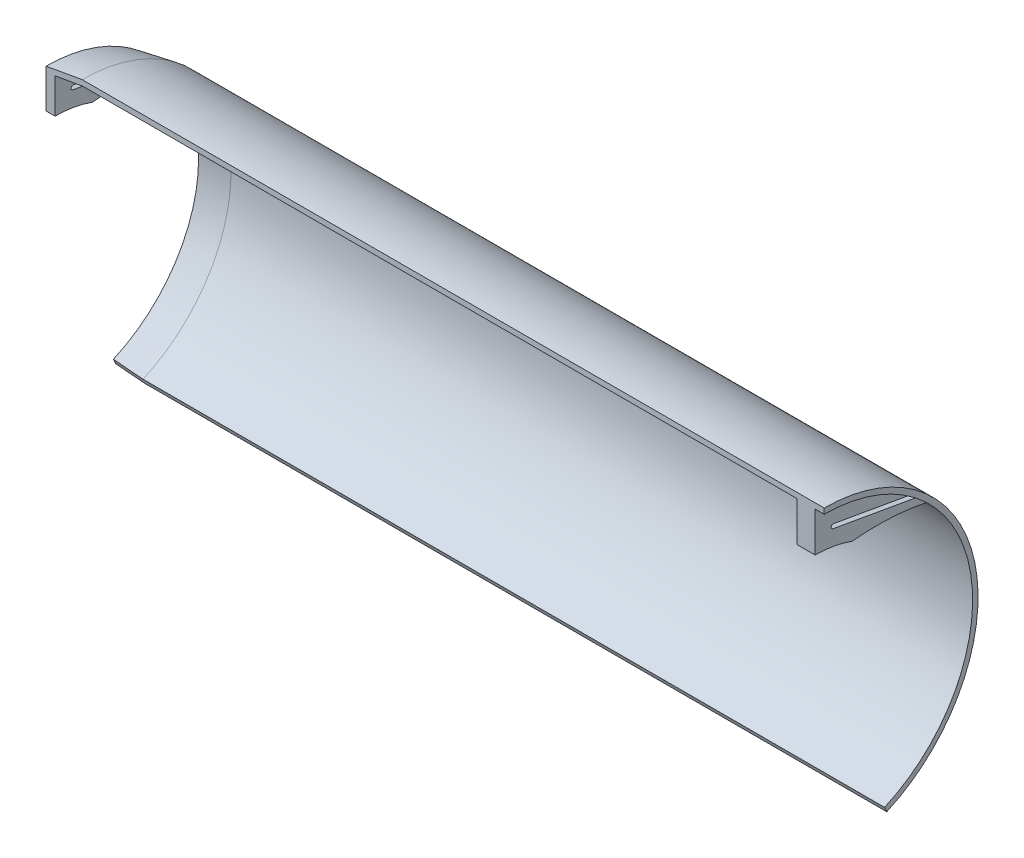
SolidWorks part; units mm, degrees
ref_plane "Front Plane" through (0, 0, 0) normal (0, 0, 1) x (1, 0, 0)
ref_plane "Top Plane" through (0, 0, 0) normal (0, 1, 0) x (1, 0, 0)
ref_plane "Right Plane" through (0, 0, 0) normal (1, 0, 0) x (0, 0, -1)
curve "Curve1"
  spline degree 3 poles (0, 0, 0) (-0.0123, 3.8916, 0) (-0.0274, 8.685, 0) (0.3616, 14.0857, 0) (0.5761, 16.0905, 0) (0.7825, 17.6048, 0) (0.9862, 18.8543, 0) (1.1887, 19.9315, 0) (1.3904, 20.8857, 0) (1.5917, 21.7465, 0) (1.7927, 22.5337, 0) (1.9935, 23.2611, 0) (2.1942, 23.9386, 0) (2.3947, 24.5739, 0) (2.5952, 25.1728, 0) (2.7956, 25.7401, 0) (2.9959, 26.2796, 0) (3.1962, 26.7943, 0) (3.3965, 27.2868, 0) (3.5967, 27.7594, 0) (3.7969, 28.2139, 0) (3.9971, 28.6519, 0) (4.1973, 29.0748, 0) (4.3974, 29.4838, 0) (4.5976, 29.8799, 0) (4.7977, 30.2641, 0) (4.9978, 30.6373, 0) (5.1979, 31.0001, 0) (5.398, 31.3533, 0) (5.5981, 31.6974, 0) (5.7982, 32.033, 0) (5.9983, 32.3606, 0) (6.1984, 32.6807, 0) (6.3985, 32.9935, 0) (6.5985, 33.2996, 0) (6.7986, 33.5993, 0) (6.9986, 33.8929, 0) (7.1987, 34.1806, 0) (7.3987, 34.4628, 0) (7.5988, 34.7397, 0) (7.7988, 35.0115, 0) (7.9989, 35.2785, 0) (8.1989, 35.5408, 0) (8.399, 35.7988, 0) (8.599, 36.0524, 0) (8.799, 36.3019, 0) (8.9991, 36.5476, 0) (9.1991, 36.7894, 0) (9.3991, 37.0275, 0) (9.5992, 37.2622, 0) (9.7992, 37.4934, 0) (9.9992, 37.7214, 0) (10.1992, 37.9461, 0) (10.3993, 38.1679, 0) (10.5993, 38.3866, 0) (10.7993, 38.6025, 0) (10.9993, 38.8156, 0) (11.1993, 39.026, 0) (11.3994, 39.2338, 0) (11.5994, 39.4391, 0) (11.7994, 39.6419, 0) (11.9994, 39.8422, 0) (12.1994, 40.0403, 0) (12.3995, 40.2361, 0) (12.5995, 40.4297, 0) (12.7995, 40.6212, 0) (12.9995, 40.8106, 0) (13.1995, 40.998, 0) (13.3995, 41.1834, 0) (13.5995, 41.3668, 0) (13.7995, 41.5484, 0) (13.9996, 41.7281, 0) (14.1996, 41.9061, 0) (14.3996, 42.0823, 0) (14.5996, 42.2568, 0) (14.7996, 42.4296, 0) (14.9996, 42.6008, 0) (15.1996, 42.7705, 0) (15.3996, 42.9385, 0) (15.5996, 43.1051, 0) (15.7996, 43.2701, 0) (15.9997, 43.4337, 0) (16.1997, 43.5959, 0) (16.3997, 43.7567, 0) (16.5997, 43.9161, 0) (16.7997, 44.0742, 0) (16.9997, 44.2309, 0) (17.1997, 44.3864, 0) (17.3997, 44.5406, 0) (17.5997, 44.6936, 0) (17.7997, 44.8453, 0) (17.9997, 44.9959, 0) (18.1997, 45.1453, 0) (18.3997, 45.2936, 0) (18.5997, 45.4407, 0) (18.7997, 45.5868, 0) (18.9997, 45.7317, 0) (19.1998, 45.8756, 0) (19.3998, 46.0185, 0) (19.5998, 46.1603, 0) (19.7998, 46.3011, 0) (19.9998, 46.4409, 0) (20.1998, 46.5797, 0) (20.3998, 46.7176, 0) (20.5998, 46.8546, 0) (20.7998, 46.9906, 0) (20.9998, 47.1257, 0) (21.1998, 47.2599, 0) (21.3998, 47.3932, 0) (21.5998, 47.5256, 0) (21.7998, 47.6572, 0) (21.9998, 47.788, 0) (22.1998, 47.9179, 0) (22.3998, 48.047, 0) (22.5998, 48.1753, 0) (22.7998, 48.3028, 0) (22.9998, 48.4295, 0) (23.1998, 48.5555, 0) (23.3998, 48.6807, 0) (23.5998, 48.8051, 0) (23.7998, 48.9288, 0) (23.9998, 49.0518, 0) (24.1998, 49.1741, 0) (24.3998, 49.2957, 0) (24.5998, 49.4165, 0) (24.7999, 49.5367, 0) (24.9999, 49.6562, 0) (25.1999, 49.7751, 0) (25.3999, 49.8933, 0) (25.5999, 50.0108, 0) (25.7999, 50.1277, 0) (25.9999, 50.2439, 0) (26.1999, 50.3596, 0) (26.3999, 50.4746, 0) (26.5999, 50.589, 0) (26.7999, 50.7028, 0) (26.9999, 50.8161, 0) (27.1999, 50.9287, 0) (27.3999, 51.0407, 0) (27.5999, 51.1522, 0) (27.7999, 51.2631, 0) (27.9999, 51.3735, 0) (28.1999, 51.4833, 0) (28.3999, 51.5926, 0) (28.5999, 51.7013, 0) (28.7999, 51.8095, 0) (28.9999, 51.9172, 0) (29.1999, 52.0243, 0) (29.3999, 52.131, 0) (29.5999, 52.2371, 0) (29.7999, 52.3428, 0) (29.9999, 52.4479, 0) (30.1999, 52.5526, 0) (30.3999, 52.6567, 0) (30.5999, 52.7604, 0) (30.7999, 52.8636, 0) (30.9999, 52.9664, 0) (31.1999, 53.0687, 0) (31.3999, 53.1705, 0) (31.5999, 53.2719, 0) (31.7999, 53.3728, 0) (31.9999, 53.4733, 0) (32.1999, 53.5733, 0) (32.3999, 53.6729, 0) (32.5999, 53.7721, 0) (32.7999, 53.8709, 0) (32.9999, 53.9692, 0) (33.1999, 54.0671, 0) (33.3999, 54.1646, 0) (33.5999, 54.2617, 0) (33.7999, 54.3584, 0) (33.9999, 54.4547, 0) (34.1999, 54.5506, 0) (34.3999, 54.6461, 0) (34.5999, 54.7412, 0) (34.7999, 54.836, 0) (34.9999, 54.9303, 0) (35.1999, 55.0243, 0) (35.3999, 55.1179, 0) (35.5999, 55.2111, 0) (35.7999, 55.304, 0) (35.9999, 55.3965, 0) (36.1999, 55.4887, 0) (36.3999, 55.5805, 0) (36.5999, 55.6719, 0) (36.7999, 55.763, 0) (36.9999, 55.8537, 0) (37.1999, 55.9441, 0) (37.3999, 56.0342, 0) (37.5999, 56.1239, 0) (37.7999, 56.2133, 0) (37.9999, 56.3024, 0) (38.1999, 56.3911, 0) (38.3999, 56.4795, 0) (38.5999, 56.5676, 0) (38.7999, 56.6554, 0) (38.9999, 56.7428, 0) (39.1999, 56.83, 0) (39.3999, 56.9168, 0) (39.5999, 57.0033, 0) (39.7999, 57.0896, 0) (39.9999, 57.1755, 0) (40.1999, 57.2611, 0) (40.3999, 57.3464, 0) (40.5999, 57.4314, 0) (40.7999, 57.5161, 0) (40.9999, 57.6006, 0) (41.1999, 57.6847, 0) (41.3999, 57.7686, 0) (41.6, 57.8522, 0) (41.8, 57.9355, 0) (42, 58.0185, 0) (42.2, 58.1012, 0) (42.4, 58.1837, 0) (42.6, 58.2659, 0) (42.8, 58.3479, 0) (43, 58.4295, 0) (43.2, 58.5109, 0) (43.4, 58.592, 0) (43.6, 58.6729, 0) (43.8, 58.7535, 0) (44, 58.8339, 0) (44.2, 58.914, 0) (44.4, 58.9938, 0) (44.6, 59.0734, 0) (44.8, 59.1528, 0) (45, 59.2319, 0) (45.2, 59.3107, 0) (45.4, 59.3893, 0) (45.6, 59.4677, 0) (45.8, 59.5458, 0) (46, 59.6237, 0) (46.2, 59.7014, 0) (46.4, 59.7788, 0) (46.6, 59.856, 0) (46.8, 59.9329, 0) (47, 60.0096, 0) (47.2, 60.0861, 0) (47.4, 60.1624, 0) (47.6, 60.2385, 0) (47.8, 60.3143, 0) (48, 60.3899, 0) (48.2, 60.4652, 0) (48.4, 60.5404, 0) (48.6, 60.6153, 0) (48.8, 60.6901, 0) (49, 60.7646, 0) (49.2, 60.8389, 0) (49.4, 60.913, 0) (49.6, 60.9869, 0) (49.8, 61.0605, 0) (50, 61.134, 0) (50.2, 61.2072, 0) (50.4, 61.2803, 0) (50.6, 61.3531, 0) (50.8, 61.4258, 0) (51, 61.4982, 0) (51.2, 61.5705, 0) (51.4, 61.6426, 0) (51.6, 61.7144, 0) (51.8, 61.7861, 0) (52, 61.8575, 0) (52.2, 61.9288, 0) (52.4, 61.9999, 0) (52.6, 62.0708, 0) (52.8, 62.1415, 0) (53, 62.212, 0) (53.2, 62.2824, 0) (53.4, 62.3525, 0) (53.6, 62.4225, 0) (53.8, 62.4923, 0) (54, 62.5619, 0) (54.2, 62.6313, 0) (54.4, 62.7006, 0) (54.6, 62.7696, 0) (54.8, 62.8385, 0) (55, 62.9072, 0) (55.2, 62.9758, 0) (55.4, 63.0441, 0) (55.6, 63.1123, 0) (55.8, 63.1803, 0) (56, 63.2482, 0) (56.2, 63.3159, 0) (56.4, 63.3834, 0) (56.6, 63.4507, 0) (56.8, 63.5179, 0) (57, 63.5849, 0) (57.2, 63.6518, 0) (57.4, 63.7185, 0) (57.6, 63.785, 0) (57.8, 63.8513, 0) (58, 63.9175, 0) (58.2, 63.9836, 0) (58.4, 64.0495, 0) (58.6, 64.1152, 0) (58.8, 64.1808, 0) (59, 64.2462, 0) (59.2, 64.3114, 0) (59.4, 64.3765, 0) (59.6, 64.4415, 0) (59.8, 64.5063, 0) (60, 64.5709, 0) (60.2, 64.6354, 0) (60.4, 64.6998, 0) (60.6, 64.764, 0) (60.8, 64.828, 0) (61, 64.8919, 0) (61.2, 64.9557, 0) (61.4, 65.0193, 0) (61.6, 65.0827, 0) (61.8, 65.1461, 0) (62, 65.2092, 0) (62.2, 65.2723, 0) (62.4, 65.3352, 0) (62.6, 65.3979, 0) (62.8, 65.4605, 0) (63, 65.523, 0) (63.2, 65.5853, 0) (63.4, 65.6475, 0) (63.6, 65.7096, 0) (63.8, 65.7715, 0) (64, 65.8333, 0) (64.2, 65.895, 0) (64.4, 65.9565, 0) (64.6, 66.0179, 0) (64.8, 66.0791, 0) (65, 66.1402, 0) (65.2, 66.2012, 0) (65.4, 66.2621, 0) (65.6, 66.3228, 0) (65.8, 66.3834, 0) (66, 66.4439, 0) (66.2, 66.5042, 0) (66.4, 66.5644, 0) (66.6, 66.6245, 0) (66.8, 66.6845, 0) (67, 66.7443, 0) (67.2, 66.804, 0) (67.4, 66.8636, 0) (67.6, 66.923, 0) (67.8, 66.9824, 0) (68, 67.0416, 0) (68.2, 67.1007, 0) (68.4, 67.1597, 0) (68.6, 67.2185, 0) (68.8, 67.2772, 0) (69, 67.3359, 0) (69.2, 67.3943, 0) (69.4, 67.4527, 0) (69.6, 67.511, 0) (69.8, 67.5691, 0) (70, 67.6271, 0) (70.2, 67.6851, 0) (70.4, 67.7428, 0) (70.6, 67.8005, 0) (70.8, 67.8581, 0) (71, 67.9155, 0) (71.2, 67.9729, 0) (71.4, 68.0301, 0) (71.6, 68.0872, 0) (71.8, 68.1442, 0) (72, 68.2011, 0) (72.2, 68.2579, 0) (72.4, 68.3145, 0) (72.6, 68.3711, 0) (72.8, 68.4276, 0) (73, 68.4839, 0) (73.2, 68.5401, 0) (73.4, 68.5963, 0) (73.6, 68.6523, 0) (73.8, 68.7082, 0) (74, 68.764, 0) (74.2, 68.8197, 0) (74.4, 68.8753, 0) (74.6, 68.9308, 0) (74.8, 68.9862, 0) (75, 69.0415, 0) (75.2, 69.0966, 0) (75.4, 69.1517, 0) (75.6, 69.2067, 0) (75.8, 69.2616, 0) (76, 69.3164, 0) (76.2, 69.371, 0) (76.4, 69.4256, 0) (76.6, 69.4801, 0) (76.8, 69.5344, 0) (77, 69.5887, 0) (77.2, 69.6429, 0) (77.4, 69.697, 0) (77.6, 69.751, 0) (77.8, 69.8048, 0) (78, 69.8586, 0) (78.2, 69.9123, 0) (78.4, 69.9659, 0) (78.6, 70.0194, 0) (78.8, 70.0728, 0) (79, 70.1261, 0) (79.2, 70.1793, 0) (79.4, 70.2324, 0) (79.6, 70.2855, 0) (79.8, 70.3384, 0) (80, 70.3912, 0) (80.2, 70.444, 0) (80.4, 70.4966, 0) (80.6, 70.5492, 0) (80.8, 70.6017, 0) (81, 70.6541, 0) (81.2, 70.7064, 0) (81.4, 70.7586, 0) (81.6, 70.8107, 0) (81.8, 70.8627, 0) (82, 70.9146, 0) (82.2, 70.9665, 0) (82.4, 71.0182, 0) (82.6, 71.0699, 0) (82.8, 71.1215, 0) (83, 71.173, 0) (83.2, 71.2244, 0) (83.4, 71.2757, 0) (83.6, 71.3269, 0) (83.8, 71.3781, 0) (84, 71.4291, 0) (84.2, 71.4801, 0) (84.4, 71.531, 0) (84.6, 71.5818, 0) (84.8, 71.6325, 0) (85, 71.6832, 0) (85.2, 71.7337, 0) (85.4, 71.7842, 0) (85.6, 71.8346, 0) (85.8, 71.8849, 0) (86, 71.9351, 0) (86.2, 71.9853, 0) (86.4, 72.0354, 0) (86.6, 72.0853, 0) (86.8, 72.1352, 0) (87, 72.1851, 0) (87.2, 72.2348, 0) (87.4, 72.2845, 0) (87.6, 72.3341, 0) (87.8, 72.3836, 0) (88, 72.433, 0) (88.2, 72.4823, 0) (88.4, 72.5316, 0) (88.6, 72.5808, 0) (88.8, 72.6299, 0) (89, 72.6789, 0) (89.2, 72.7279, 0) (89.4, 72.7768, 0) (89.6, 72.8256, 0) (89.8, 72.8743, 0) (90, 72.923, 0) (90.2, 72.9716, 0) (90.4, 73.0201, 0) (90.6, 73.0685, 0) (90.8, 73.1168, 0) (91, 73.1651, 0) (91.2, 73.2133, 0) (91.4, 73.2614, 0) (91.6, 73.3095, 0) (91.8, 73.3575, 0) (92, 73.4054, 0) (92.2, 73.4532, 0) (92.4, 73.501, 0) (92.6, 73.5487, 0) (92.8, 73.5963, 0) (93, 73.6439, 0) (93.2, 73.6913, 0) (93.4, 73.7387, 0) (93.6, 73.7861, 0) (93.8, 73.8333, 0) (94, 73.8805, 0) (94.2, 73.9276, 0) (94.4, 73.9747, 0) (94.6, 74.0217, 0) (94.8, 74.0686, 0) (95, 74.1154, 0) (95.2, 74.1622, 0) (95.4, 74.2089, 0) (95.6, 74.2556, 0) (95.8, 74.3021, 0) (96, 74.3486, 0) (96.2, 74.3951, 0) (96.4, 74.4414, 0) (96.6, 74.4877, 0) (96.8, 74.534, 0) (97, 74.5801, 0) (97.2, 74.6262, 0) (97.4, 74.6723, 0) (97.6, 74.7182, 0) (97.8, 74.7641, 0) (98, 74.81, 0) (98.2, 74.8557, 0) (98.4, 74.9014, 0) (98.6, 74.9471, 0) (98.8, 74.9926, 0) (99, 75.0382, 0) (99.2, 75.0836, 0) (99.4, 75.129, 0) (99.6, 75.1743, 0) (99.8, 75.2196, 0) (100, 75.2647, 0) (100.2, 75.3099, 0) (100.4, 75.3549, 0) (100.6, 75.3999, 0) (100.8, 75.4449, 0) (101, 75.4898, 0) (101.2, 75.5346, 0) (101.4, 75.5793, 0) (101.6, 75.624, 0) (101.8, 75.6686, 0) (102, 75.7132, 0) (102.2, 75.7577, 0) (102.4, 75.8022, 0) (102.6, 75.8465, 0) (102.8, 75.8909, 0) (103, 75.9351, 0) (103.2, 75.9793, 0) (103.4, 76.0235, 0) (103.6, 76.0676, 0) (103.8, 76.1116, 0) (104, 76.1556, 0) (104.2, 76.1995, 0) (104.4, 76.2433, 0) (104.6, 76.2871, 0) (104.8, 76.3308, 0) (105, 76.3745, 0) (105.2, 76.4181, 0) (105.4, 76.4617, 0) (105.6, 76.5052, 0) (105.8, 76.5486, 0) (106, 76.592, 0) (106.2, 76.6353, 0) (106.4, 76.6786, 0) (106.6, 76.7218, 0) (106.8, 76.7649, 0) (107, 76.808, 0) (107.2, 76.8511, 0) (107.4, 76.8941, 0) (107.6, 76.937, 0) (107.8, 76.9799, 0) (108, 77.0227, 0) (108.2, 77.0655, 0) (108.4, 77.1082, 0) (108.6, 77.1508, 0) (108.8, 77.1934, 0) (109, 77.236, 0) (109.2, 77.2784, 0) (109.4, 77.3209, 0) (109.6, 77.3633, 0) (109.8, 77.4056, 0) (110, 77.4479, 0) (110.2, 77.4901, 0) (110.4, 77.5322, 0) (110.6, 77.5743, 0) (110.8, 77.6164, 0) (111, 77.6584, 0) (111.2, 77.7004, 0) (111.4, 77.7423, 0) (111.6, 77.7841, 0) (111.8, 77.8259, 0) (112, 77.8676, 0) (112.2, 77.9093, 0) (112.4, 77.951, 0) (112.6, 77.9925, 0) (112.8, 78.0341, 0) (113, 78.0756, 0) (113.2, 78.117, 0) (113.4, 78.1584, 0) (113.6, 78.1997, 0) (113.8, 78.241, 0) (114, 78.2822, 0) (114.2, 78.3234, 0) (114.4, 78.3645, 0) (114.6, 78.4056, 0) (114.8, 78.4466, 0) (115, 78.4876, 0) (115.2, 78.5285, 0) (115.4, 78.5694, 0) (115.6, 78.6102, 0) (115.8, 78.651, 0) (116, 78.6917, 0) (116.2, 78.7324, 0) (116.4, 78.773, 0) (116.6, 78.8136, 0) (116.8, 78.8541, 0) (117, 78.8946, 0) (117.2, 78.935, 0) (117.4, 78.9754, 0) (117.6, 79.0158, 0) (117.8, 79.0561, 0) (118, 79.0963, 0) (118.2, 79.1365, 0) (118.4, 79.1766, 0) (118.6, 79.2167, 0) (118.8, 79.2568, 0) (119, 79.2968, 0) (119.2, 79.3368, 0) (119.4, 79.3767, 0) (119.6, 79.4165, 0) (119.8, 79.4564, 0) (120, 79.4961, 0) (120.2, 79.5358, 0) (120.4, 79.5755, 0) (120.6, 79.6152, 0) (120.8, 79.6547, 0) (121, 79.6943, 0) (121.2, 79.7338, 0) (121.4, 79.7732, 0) (121.6, 79.8126, 0) (121.8, 79.852, 0) (122, 79.8913, 0) (122.2, 79.9306, 0) (122.4, 79.9698, 0) (122.6, 80.009, 0) (122.8, 80.0481, 0) (123, 80.0872, 0) (123.2, 80.1262, 0) (123.4, 80.1652, 0) (123.6, 80.2042, 0) (123.8, 80.2431, 0) (124, 80.282, 0) (124.2, 80.3208, 0) (124.4, 80.3596, 0) (124.6, 80.3983, 0) (124.8, 80.437, 0) (125, 80.4757, 0) (125.2, 80.5143, 0) (125.4, 80.5528, 0) (125.6, 80.5914, 0) (125.8, 80.6298, 0) (126, 80.6683, 0) (126.2, 80.7067, 0) (126.4, 80.745, 0) (126.6, 80.7833, 0) (126.8, 80.8216, 0) (127, 80.8598, 0) (127.2, 80.898, 0) (127.4, 80.9361, 0) (127.6, 80.9742, 0) (127.8, 81.0123, 0) (128, 81.0503, 0) (128.2, 81.0883, 0) (128.4, 81.1262, 0) (128.6, 81.1641, 0) (128.8, 81.2019, 0) (129, 81.2397, 0) (129.2, 81.2775, 0) (129.4, 81.3152, 0) (129.6, 81.3529, 0) (129.8, 81.3906, 0) (130, 81.4282, 0) (130.2, 81.4657, 0) (130.4, 81.5032, 0) (130.6, 81.5407, 0) (130.8, 81.5782, 0) (131, 81.6156, 0) (131.2, 81.6529, 0) (131.4, 81.6902, 0) (131.6, 81.7275, 0) (131.8, 81.7648, 0) (132, 81.802, 0) (132.2, 81.8391, 0) (132.4, 81.8763, 0) (132.6, 81.9133, 0) (132.8, 81.9504, 0) (133, 81.9874, 0) (133.2, 82.0244, 0) (133.4, 82.0613, 0) (133.6, 82.0982, 0) (133.8, 82.135, 0) (134, 82.1718, 0) (134.2, 82.2086, 0) (134.4, 82.2454, 0) (134.6, 82.282, 0) (134.8, 82.3187, 0) (135, 82.3553, 0) (135.2, 82.3919, 0) (135.4, 82.4285, 0) (135.6, 82.465, 0) (135.8, 82.5014, 0) (136, 82.5379, 0) (136.2, 82.5743, 0) (136.4, 82.6106, 0) (136.6, 82.6469, 0) (136.8, 82.6832, 0) (137, 82.7195, 0) (137.2, 82.7557, 0) (137.4, 82.7919, 0) (137.6, 82.828, 0) (137.8, 82.8641, 0) (138, 82.9001, 0) (138.2, 82.9362, 0) (138.4, 82.9722, 0) (138.6, 83.0081, 0) (138.8, 83.044, 0) (139, 83.0799, 0) (139.2, 83.1158, 0) (139.4, 83.1516, 0) (139.6, 83.1873, 0) (139.8, 83.2231, 0) (140, 83.2588, 0) (140.2, 83.2944, 0) (140.4, 83.3301, 0) (140.6, 83.3657, 0) (140.8, 83.4012, 0) (141, 83.4367, 0) (141.2, 83.4722, 0) (141.4, 83.5077, 0) (141.6, 83.5431, 0) (141.8, 83.5785, 0) (142, 83.6138, 0) (142.2, 83.6491, 0) (142.4, 83.6844, 0) (142.6, 83.7197, 0) (142.8, 83.7549, 0) (143, 83.79, 0) (143.2, 83.8252, 0) (143.4, 83.8603, 0) (143.6, 83.8954, 0) (143.8, 83.9304, 0) (144, 83.9654, 0) (144.2, 84.0004, 0) (144.4, 84.0353, 0) (144.6, 84.0702, 0) (144.8, 84.1051, 0) (145, 84.1399, 0) (145.2, 84.1747, 0) (145.4, 84.2095, 0) (145.6, 84.2442, 0) (145.8, 84.2789, 0) (146, 84.3136, 0) (146.2, 84.3482, 0) (146.4, 84.3828, 0) (146.6, 84.4174, 0) (146.8, 84.4519, 0) (147, 84.4864, 0) (147.2, 84.5209, 0) (147.4, 84.5553, 0) (147.6, 84.5897, 0) (147.8, 84.6241, 0) (148, 84.6584, 0) (148.2, 84.6927, 0) (148.4, 84.727, 0) (148.6, 84.7612, 0) (148.8, 84.7954, 0) (149, 84.8296, 0) (149.2, 84.8638, 0) (149.4, 84.8979, 0) (149.6, 84.9319, 0) (149.8, 84.966, 0) (149.9333, 84.9887, 0) (150, 85, 0) knots 0 0 0 0 0.061462 0.075706 0.085548 0.093322 0.099856 0.105554 0.110643 0.115268 0.119525 0.123482 0.127192 0.130691 0.13401 0.137173 0.140199 0.143104 0.145901 0.148602 0.151215 0.15375 0.156213 0.158609 0.160946 0.163227 0.165456 0.167638 0.169775 0.171871 0.173928 0.17595 0.177937 0.179893 0.181819 0.183716 0.185587 0.187433 0.189255 0.191054 0.192831 0.194589 0.196326 0.198045 0.199747 0.201431 0.2031 0.204753 0.206391 0.208015 0.209626 0.211223 0.212808 0.214381 0.215942 0.217493 0.219032 0.220561 0.22208 0.22359 0.225091 0.226582 0.228065 0.229539 0.231006 0.232464 0.233915 0.235359 0.236795 0.238225 0.239648 0.241065 0.242475 0.243879 0.245277 0.24667 0.248057 0.249438 0.250814 0.252185 0.253551 0.254913 0.256269 0.257621 0.258968 0.260311 0.26165 0.262984 0.264315 0.265641 0.266964 0.268282 0.269598 0.270909 0.272217 0.273522 0.274823 0.276121 0.277416 0.278707 0.279996 0.281281 0.282564 0.283843 0.28512 0.286394 0.287666 0.288935 0.290201 0.291465 0.292726 0.293985 0.295241 0.296495 0.297747 0.298996 0.300243 0.301489 0.302732 0.303972 0.305211 0.306448 0.307683 0.308916 0.310147 0.311376 0.312604 0.313829 0.315053 0.316275 0.317495 0.318714 0.319931 0.321147 0.32236 0.323573 0.324783 0.325993 0.3272 0.328406 0.329611 0.330815 0.332017 0.333217 0.334416 0.335614 0.336811 0.338006 0.3392 0.340393 0.341584 0.342775 0.343964 0.345152 0.346339 0.347524 0.348709 0.349892 0.351074 0.352256 0.353436 0.354615 0.355793 0.35697 0.358146 0.359321 0.360495 0.361668 0.36284 0.364011 0.365182 0.366351 0.36752 0.368687 0.369854 0.37102 0.372185 0.373349 0.374512 0.375674 0.376836 0.377997 0.379157 0.380316 0.381475 0.382632 0.383789 0.384946 0.386101 0.387256 0.38841 0.389563 0.390716 0.391868 0.393019 0.39417 0.39532 0.396469 0.397618 0.398766 0.399913 0.40106 0.402206 0.403351 0.404496 0.40564 0.406784 0.407927 0.409069 0.410211 0.411353 0.412493 0.413633 0.414773 0.415912 0.417051 0.418189 0.419326 0.420463 0.4216 0.422736 0.423871 0.425006 0.426141 0.427275 0.428408 0.429541 0.430674 0.431806 0.432937 0.434068 0.435199 0.436329 0.437459 0.438588 0.439717 0.440846 0.441974 0.443101 0.444229 0.445355 0.446482 0.447608 0.448733 0.449858 0.450983 0.452107 0.453231 0.454355 0.455478 0.456601 0.457723 0.458845 0.459967 0.461088 0.462209 0.46333 0.46445 0.46557 0.46669 0.467809 0.468928 0.470046 0.471164 0.472282 0.4734 0.474517 0.475634 0.47675 0.477866 0.478982 0.480098 0.481213 0.482328 0.483443 0.484557 0.485671 0.486785 0.487898 0.489011 0.490124 0.491237 0.492349 0.493461 0.494573 0.495684 0.496796 0.497906 0.499017 0.500127 0.501237 0.502347 0.503457 0.504566 0.505675 0.506784 0.507892 0.509001 0.510109 0.511216 0.512324 0.513431 0.514538 0.515645 0.516752 0.517858 0.518964 0.52007 0.521175 0.522281 0.523386 0.524491 0.525595 0.5267 0.527804 0.528908 0.530012 0.531116 0.532219 0.533322 0.534425 0.535528 0.53663 0.537733 0.538835 0.539937 0.541038 0.54214 0.543241 0.544342 0.545443 0.546544 0.547644 0.548745 0.549845 0.550945 0.552044 0.553144 0.554243 0.555342 0.556441 0.55754 0.558639 0.559737 0.560836 0.561934 0.563032 0.564129 0.565227 0.566324 0.567421 0.568518 0.569615 0.570712 0.571809 0.572905 0.574001 0.575097 0.576193 0.577289 0.578384 0.57948 0.580575 0.58167 0.582765 0.58386 0.584954 0.586049 0.587143 0.588237 0.589331 0.590425 0.591519 0.592612 0.593706 0.594799 0.595892 0.596985 0.598078 0.59917 0.600263 0.601355 0.602448 0.60354 0.604632 0.605724 0.606815 0.607907 0.608998 0.61009 0.611181 0.612272 0.613363 0.614453 0.615544 0.616635 0.617725 0.618815 0.619905 0.620995 0.622085 0.623175 0.624265 0.625354 0.626443 0.627533 0.628622 0.629711 0.6308 0.631888 0.632977 0.634066 0.635154 0.636242 0.637331 0.638419 0.639507 0.640594 0.641682 0.64277 0.643857 0.644945 0.646032 0.647119 0.648206 0.649293 0.65038 0.651467 0.652553 0.65364 0.654726 0.655813 0.656899 0.657985 0.659071 0.660157 0.661243 0.662328 0.663414 0.664499 0.665585 0.66667 0.667755 0.66884 0.669925 0.67101 0.672095 0.67318 0.674264 0.675349 0.676433 0.677518 0.678602 0.679686 0.68077 0.681854 0.682938 0.684022 0.685105 0.686189 0.687272 0.688356 0.689439 0.690522 0.691605 0.692688 0.693771 0.694854 0.695937 0.69702 0.698102 0.699185 0.700267 0.70135 0.702432 0.703514 0.704596 0.705678 0.70676 0.707842 0.708924 0.710006 0.711087 0.712169 0.71325 0.714332 0.715413 0.716494 0.717575 0.718656 0.719737 0.720818 0.721899 0.72298 0.724061 0.725141 0.726222 0.727302 0.728382 0.729463 0.730543 0.731623 0.732703 0.733783 0.734863 0.735943 0.737023 0.738103 0.739182 0.740262 0.741341 0.742421 0.7435 0.744579 0.745659 0.746738 0.747817 0.748896 0.749975 0.751054 0.752133 0.753211 0.75429 0.755369 0.756447 0.757526 0.758604 0.759682 0.760761 0.761839 0.762917 0.763995 0.765073 0.766151 0.767229 0.768307 0.769385 0.770462 0.77154 0.772618 0.773695 0.774773 0.77585 0.776927 0.778005 0.779082 0.780159 0.781236 0.782313 0.78339 0.784467 0.785544 0.786621 0.787698 0.788774 0.789851 0.790928 0.792004 0.793081 0.794157 0.795233 0.79631 0.797386 0.798462 0.799538 0.800614 0.80169 0.802766 0.803842 0.804918 0.805994 0.80707 0.808145 0.809221 0.810296 0.811372 0.812447 0.813523 0.814598 0.815674 0.816749 0.817824 0.818899 0.819974 0.821049 0.822124 0.823199 0.824274 0.825349 0.826424 0.827499 0.828573 0.829648 0.830723 0.831797 0.832872 0.833946 0.835021 0.836095 0.837169 0.838244 0.839318 0.840392 0.841466 0.84254 0.843614 0.844688 0.845762 0.846836 0.84791 0.848984 0.850058 0.851131 0.852205 0.853279 0.854352 0.855426 0.856499 0.857573 0.858646 0.859719 0.860793 0.861866 0.862939 0.864012 0.865085 0.866159 0.867232 0.868305 0.869378 0.87045 0.871523 0.872596 0.873669 0.874742 0.875814 0.876887 0.87796 0.879032 0.880105 0.881177 0.88225 0.883322 0.884395 0.885467 0.886539 0.887611 0.888684 0.889756 0.890828 0.8919 0.892972 0.894044 0.895116 0.896188 0.89726 0.898332 0.899404 0.900475 0.901547 0.902619 0.90369 0.904762 0.905834 0.906905 0.907977 0.909048 0.91012 0.911191 0.912262 0.913334 0.914405 0.915476 0.916548 0.917619 0.91869 0.919761 0.920832 0.921903 0.922974 0.924045 0.925116 0.926187 0.927258 0.928329 0.929399 0.93047 0.931541 0.932612 0.933682 0.934753 0.935823 0.936894 0.937965 0.939035 0.940105 0.941176 0.942246 0.943317 0.944387 0.945457 0.946527 0.947598 0.948668 0.949738 0.950808 0.951878 0.952948 0.954018 0.955088 0.956158 0.957228 0.958298 0.959368 0.960438 0.961508 0.962577 0.963647 0.964717 0.965786 0.966856 0.967926 0.968995 0.970065 0.971134 0.972204 0.973273 0.974343 0.975412 0.976481 0.977551 0.97862 0.979689 0.980759 0.981828 0.982897 0.983966 0.985035 0.986104 0.987173 0.988242 0.989311 0.99038 0.991449 0.992518 0.993587 0.994656 0.995725 0.996794 0.997863 0.998931 1 1 1 1
sketch "Sketch1" plane through (0, 0, 0) normal (0, 0, 1) x (1, 0, 0)
  line L0 (150, 85) -> (560, 85)
  line L1 (150.2533, 82) -> (560, 82)
  line L2 (560, 85) -> (560, 82)
  line L3 (0, 0) -> (3, 0)
  line L4 (3, 0.0095) -> (3, 0)
  line L5 (3, 0) -> (560, 0) construction
  line L6 (560, 0) -> (560, 82) construction
  line L8 (140, -75) -> (540, -75) construction
  line L9 (130, 78.3755) -> (135, 78.3755)
  line L10 (140, -75) -> (140, 75) construction
  line L11 (140, 75) -> (540, 75) construction
  line L12 (135, 79.3054) -> (135, 60)
  line L13 (135, 60) -> (130, 60)
  line L14 (130, 60) -> (130, 81.4281)
  line L15 (555, 60) -> (555, 82)
  line L16 (545, 82) -> (545, 60)
  line L17 (545, 60) -> (555, 60)
  line L18 (540, -75) -> (540, 75) construction
  line L19 (140, -75) -> (540, 75) construction
  line L20 (140, 75) -> (540, -75) construction
  spline S0 degree 3 poles (-1988.6566, -159.7184) (98.3599, -158.1291) (-5.7084, -70.1856) (0.3616, 14.0857) (0.5761, 16.0905) (0.7825, 17.6048) (0.9862, 18.8543) (1.1887, 19.9315) (1.3904, 20.8857) (1.5917, 21.7465) (1.7927, 22.5337) (1.9935, 23.2611) (2.2538, 24.14) (2.5806, 25.1462) (2.9836, 26.2595) (3.3859, 27.2713) (3.7877, 28.2016) (4.1891, 29.0648) (4.5903, 29.8717) (5.0533, 30.7478) (5.5832, 31.6835) (6.1854, 32.6697) (6.7872, 33.5906) (7.4515, 34.5461) (8.1828, 35.531) (8.9851, 36.54) (9.8503, 37.5625) (10.7826, 38.5957) (11.785, 39.6369) (12.851, 40.6804) (13.984, 41.7246) (15.1862, 42.7682) (16.388, 43.7553) (17.6544, 44.7435) (18.9876, 45.7315) (20.3892, 46.7179) (21.7905, 47.6579) (23.2571, 48.5984) (24.7904, 49.5382) (26.3916, 50.4762) (28.0583, 51.4122) (29.7917, 52.3451) (31.5927, 53.2742) (33.4594, 54.1996) (35.3929, 55.1207) (37.4597, 56.0672) (39.5933, 57.0066) (41.8602, 57.9666) (44.1937, 58.9175) (46.6606, 59.8853) (49.2604, 60.8677) (51.994, 61.8617) (54.861, 62.8656) (57.7946, 63.8556) (60.8615, 64.8536) (64.0615, 65.8584) (67.4615, 66.8882) (70.9951, 67.9202) (74.6621, 68.9539) (78.4621, 69.9886) (82.4622, 71.0404) (86.6623, 72.1071) (91.0624, 73.1864) (95.6625, 74.2764) (100.4626, 75.3753) (105.4628, 76.4816) (110.6629, 77.5938) (116.063, 78.7107) (121.6632, 79.8312) (127.5299, 80.9671) (133.6633, 82.1162) (140.0634, 83.2764) (145.1985, 84.1774) (148.3332, 84.7158) (149.3333, 84.8865) (149.6, 84.9319) (194.4783, 92.5723) (239.7917, 97.2513) (-50.3187, 2073.1568) knots -1.249314 -1.249314 -1.249314 -1.249314 0.061462 0.075706 0.085548 0.093322 0.099856 0.105554 0.110643 0.115268 0.119525 0.123482 0.127192 0.13401 0.140199 0.145901 0.151215 0.156213 0.160946 0.165456 0.171871 0.177937 0.183716 0.189255 0.196326 0.2031 0.209626 0.217493 0.225091 0.232464 0.241065 0.249438 0.257621 0.265641 0.274823 0.283843 0.292726 0.301489 0.311376 0.321147 0.330815 0.341584 0.352256 0.36284 0.374512 0.386101 0.398766 0.411353 0.425006 0.438588 0.453231 0.468928 0.484557 0.501237 0.517858 0.535528 0.554243 0.574001 0.593706 0.614453 0.636242 0.659071 0.682938 0.707842 0.733783 0.760761 0.788774 0.817824 0.84791 0.879032 0.912262 0.946527 0.981828 0.994656 0.996794 0.997863 0.998931 1.716252 1.716252 1.716252 1.716252 only from (0, 0) to (150, 85) construction
  spline S1 degree 3 poles (0, 0) (-0.0123, 3.8916) (-0.0274, 8.685) (0.3616, 14.0857) (0.5761, 16.0905) (0.7825, 17.6048) (0.9862, 18.8543) (1.1887, 19.9315) (1.3904, 20.8857) (1.5917, 21.7465) (1.7927, 22.5337) (1.9935, 23.2611) (2.2538, 24.14) (2.5806, 25.1462) (2.9836, 26.2595) (3.3859, 27.2713) (3.7877, 28.2016) (4.1891, 29.0648) (4.5903, 29.8717) (5.0533, 30.7478) (5.5832, 31.6835) (6.1854, 32.6697) (6.7872, 33.5906) (7.4515, 34.5461) (8.1828, 35.531) (8.9851, 36.54) (9.8503, 37.5625) (10.7826, 38.5957) (11.785, 39.6369) (12.851, 40.6804) (13.984, 41.7246) (15.1862, 42.7682) (16.388, 43.7553) (17.6544, 44.7435) (18.9876, 45.7315) (20.3892, 46.7179) (21.7905, 47.6579) (23.2571, 48.5984) (24.7904, 49.5382) (26.3916, 50.4762) (28.0583, 51.4122) (29.7917, 52.3451) (31.5927, 53.2742) (33.4594, 54.1996) (35.3929, 55.1207) (37.4597, 56.0672) (39.5933, 57.0066) (41.8602, 57.9666) (44.1937, 58.9175) (46.6606, 59.8853) (49.2604, 60.8677) (51.994, 61.8617) (54.861, 62.8656) (57.7946, 63.8556) (60.8615, 64.8536) (64.0615, 65.8584) (67.4615, 66.8882) (70.9951, 67.9202) (74.6621, 68.9539) (78.4621, 69.9886) (82.4622, 71.0404) (86.6623, 72.1071) (91.0624, 73.1864) (95.6625, 74.2764) (100.4626, 75.3753) (105.4628, 76.4816) (110.6629, 77.5938) (116.063, 78.7107) (121.6632, 79.8312) (127.5299, 80.9671) (133.6633, 82.1162) (140.0634, 83.2764) (145.1985, 84.1774) (148.3332, 84.7158) (149.4, 84.8979) (149.7333, 84.9547) (149.9333, 84.9887) (150, 85) knots 0 0 0 0 0.061462 0.075706 0.085548 0.093322 0.099856 0.105554 0.110643 0.115268 0.119525 0.123482 0.127192 0.13401 0.140199 0.145901 0.151215 0.156213 0.160946 0.165456 0.171871 0.177937 0.183716 0.189255 0.196326 0.2031 0.209626 0.217493 0.225091 0.232464 0.241065 0.249438 0.257621 0.265641 0.274823 0.283843 0.292726 0.301489 0.311376 0.321147 0.330815 0.341584 0.352256 0.36284 0.374512 0.386101 0.398766 0.411353 0.425006 0.438588 0.453231 0.468928 0.484557 0.501237 0.517858 0.535528 0.554243 0.574001 0.593706 0.614453 0.636242 0.659071 0.682938 0.707842 0.733783 0.760761 0.788774 0.817824 0.84791 0.879032 0.912262 0.946527 0.981828 0.994656 0.996794 0.998931 1 1 1 1
  spline S4 degree 1 poles (3, 0.0095) (150.2533, 82) knots 0 0 1 1 construction
  spline S5 degree 3 poles (3, 0.0095) (2.9938, 1.9694) (2.982, 5.9112) (3.1447, 11.6915) (3.6709, 17.3262) (4.8192, 22.7297) (6.752, 27.816) (10.434, 34.0689) (16.886, 40.7698) (26.3115, 47.2193) (36.5885, 52.5329) (47.3393, 57.0416) (62.0527, 62.2707) (80.8898, 67.7174) (103.8331, 73.1782) (119.8433, 76.4414) (128.9979, 78.1869) (130.8328, 78.5327) (132.4993, 78.8436) (134.1662, 79.1526) (140.0771, 80.2373) (145.5819, 81.205) (150.2533, 82) knots 0 0 0 0 0.031208 0.062417 0.093625 0.124833 0.156041 0.18725 0.249666 0.312083 0.374499 0.436916 0.499332 0.624165 0.748998 0.873831 0.883277 0.89671 0.903427 0.910144 0.923577 0.998664 0.998664 0.998664 0.998664
  point P8 (340, 0)
  dimension "D2" = 410
  dimension "D1" = 5
  dimension "D7" = 10
  dimension "D9" = 10
  dimension "D4" = 20
  dimension "D5" = 5
  dimension "D6" = 400
  dimension "D10" = 150
  dimension "D8" = 120
  dimension "D3" = 3
revolve "Revolve5" add sketch "Sketch1" angle 156 about L5 region at (344.8477, 83.4159, 0) region at (133.3296, 78.6861, 0) region at (132.5, 69.1877, 0) region at (550, 71, 0) reverse direction yes
ref_axis "Axis1" through (150, -77.6514, -34.5726) along (1, 0, 0)
ref_plane "Plane1" through (135, 0, 0) normal (1, 0, 0) x (0, 0, -1)
sketch "Sketch4" plane through (135, 0, 0) normal (-1, 0, 0) x (0, 0, 1)
  line L0 (0, 0) -> (-28.1672, 77.3887) construction
  line L1 (0, -89.4583) -> (0, 89.4583) construction
  line L2 (0, 60) -> (0, 82.3553)
  line L6 (0, 0) -> (-10.4189, 59.0885) construction
  line L7 (-57.113, 59.3338) -> (-9.8003, 67.6764)
  line L8 (-53.9452, 62.2279) -> (-10.1997, 69.9414)
  arc A1 (0, 82.3553) -> (-33.4969, -75.2353) centre (0, 0) ccw
  arc A2 (0, 82.3553) -> (-53.9452, 62.2279) centre (0, 0) ccw
  arc A5 (0, 60) -> (-24.4042, -54.8127) centre (0, 0) ccw construction
  arc A8 (0, 60) -> (-20.5212, 56.3816) centre (0, 0) ccw
  arc A9 (-9.8003, 67.6764) -> (-10.1997, 69.9414) centre (-10, 68.8089) ccw
  arc A10 (-20.5212, 56.3816) -> (-61.9052, 54.3153) centre (-34.5726, -77.6514) ccw
  arc A11 (-57.113, 59.3338) -> (-61.9052, 54.3153) centre (0, 0) ccw
  point P5 (-10.4189, 59.0885)
  point P14 (-20.5212, 56.3816)
  dimension "D2" = 8.35
  dimension "D3" = 2.3
  dimension "D4" = 10
  dimension "D1" = 20
extrude "Cut-Extrude2" cut sketch "Sketch4" along normal blind 170 flip side to cut
sketch "Sketch5" plane through (555, 0, 0) normal (1, 0, 0) x (0, 0, -1)
  line L0 (9.8003, 67.6764) -> (51.4774, 60.3275) construction
  line L1 (47.7475, 63.3207) -> (10.1997, 69.9414) construction
  line L6 (0, 85) -> (0, 82)
  line L8 (33.3524, -74.9107) -> (34.5726, -77.6514)
  line L9 (0, 85) -> (0, 60)
  line L10 (33.3524, -74.9107) -> (34.5726, -77.6514)
  line L11 (9.8003, 67.6764) -> (56.4827, 59.445)
  line L12 (53.2601, 62.3487) -> (10.1997, 69.9414)
  arc A0 (20.5212, 56.3816) -> (0, 60) centre (0, 0) ccw construction
  arc A1 (56.887, 55.2559) -> (20.5212, 56.3816) centre (34.5726, -77.6514) ccw construction
  arc A2 (33.3524, -74.9107) -> (0, 82) centre (0, 0) ccw
  arc A3 (34.5726, -77.6514) -> (0, 85) centre (0, 0) ccw
  arc A4 (33.3524, -74.9107) -> (61.3267, 54.4338) centre (0, 0) ccw
  arc A9 (34.5726, -77.6514) -> (0, 85) centre (0, 0) ccw
  arc A23 (10.1997, 69.9414) -> (9.8003, 67.6764) centre (10, 68.8089) ccw construction
  arc A24 (20.5212, 56.3816) -> (0, 60) centre (0, 0) ccw
  arc A27 (61.3267, 54.4338) -> (20.5212, 56.3816) centre (34.5726, -77.6514) ccw
  arc A34 (10.1997, 69.9414) -> (9.8003, 67.6764) centre (10, 68.8089) ccw
  arc A35 (56.4827, 59.445) -> (53.2601, 62.3487) centre (0, 0) ccw
  dimension "D1" = 0
extrude "Cut-Extrude3" cut sketch "Sketch5" against normal blind 10 and the other way through all flip side to cut
equation "\"CanSat_Len\"= 400mm"
equation "\"CanSat_Dia\"= 150mm"
equation "\"BodyTube_ID\"= 114mm"
equation "\"BodyTube_OD\"= 120mm"
equation "\"PayLoadBay_ID\"= 164mm"
equation "\"PayLoadBay_OD\"= 170mm"
equation "\"ParachuteBay_Pitch\"= 300mm"
equation "\"ElectronicsTray_PitchDist\"= 40mm"
equation "\"ElectronicsTray_Height\"= 120mm"
equation "\"MotorDia\"= 98mm"
equation "\"MotorLen\"= 289mm"
equation "\"NosePlateDia\"= 156.6mm"
equation "\"D10@Sketch1\"=\"CanSat_Dia\""
equation "\"D6@Sketch1\"=\"CanSat_Len\""
